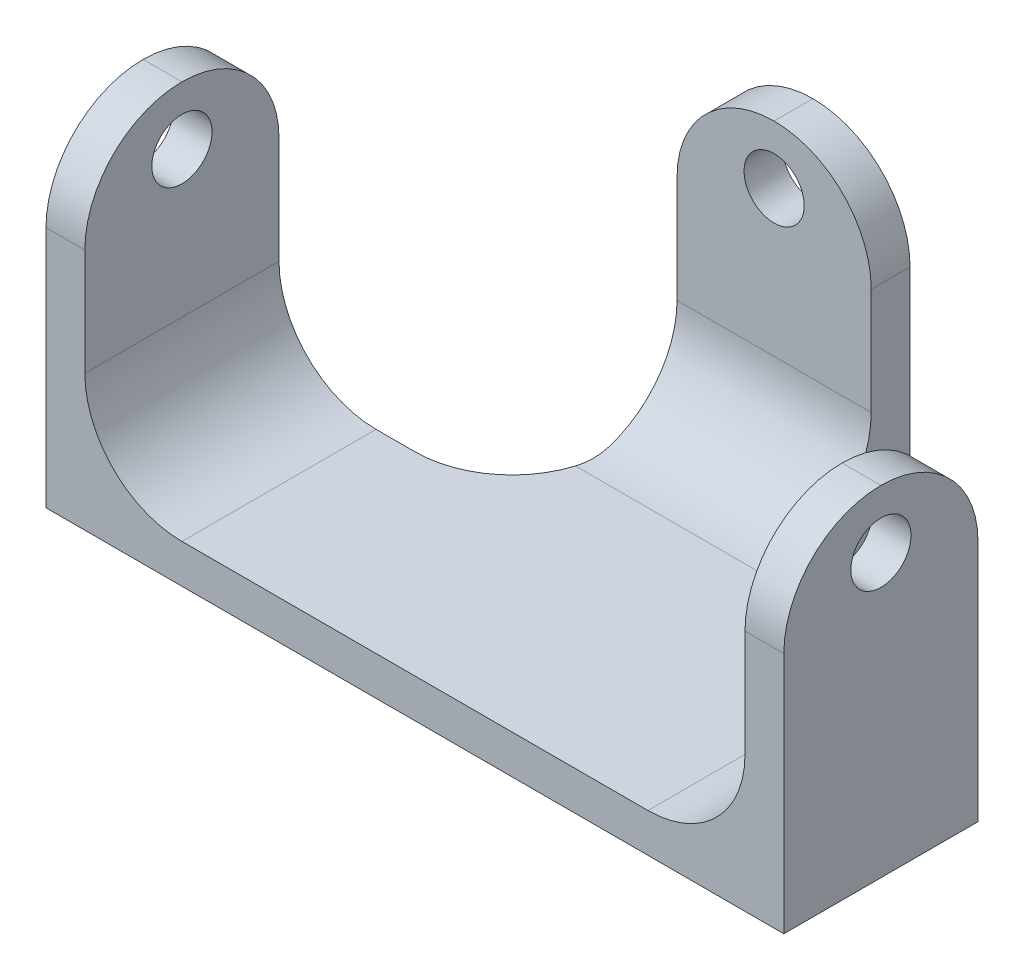
SolidWorks part; units mm, degrees
ref_plane "Front Plane" through (0, 0, 0) normal (0, 0, 1) x (1, 0, 0)
ref_plane "Top Plane" through (0, 0, 0) normal (0, 1, 0) x (1, 0, 0)
ref_plane "Right Plane" through (0, 0, 0) normal (1, 0, 0) x (0, 0, -1)
sketch "Sketch1" plane through (0, 0, 0) normal (0, 0, 1) x (1, 0, 0)
  line L0 (-10.6394, 6.8175) -> (-6.6394, 6.8175)
  line L1 (-6.6394, 6.8175) -> (-6.6394, -24.1825)
  line L2 (-6.6394, -24.1825) -> (61.3606, -24.1825)
  line L3 (61.3606, -24.1825) -> (61.3606, 6.8175)
  line L4 (61.3606, 6.8175) -> (65.3606, 6.8175)
  line L5 (65.3606, 6.8175) -> (65.3606, -28.1825)
  line L6 (65.3606, -28.1825) -> (-10.6394, -28.1825)
  line L7 (-10.6394, -28.1825) -> (-10.6394, 6.8175)
  point P6 (-2.0292, 4.2751)
  point P9 (-4.9784, 7.0209)
  point P10 (-6.6394, 6.8175)
  point P11 (-10.6394, -2.674)
  point P12 (-4.9106, -0.7757)
  point P13 (0.3775, -2.7757)
  point P14 (2.2419, 6.7497)
  dimension "D1" = 4
  dimension "D2" = 35
  dimension "D3" = 4
  dimension "D4" = 68
extrude "Boss-Extrude1" add sketch "Sketch1" along normal blind 62
sketch "Sketch2" plane through (0, -24.1825, 0) normal (0, 1, 0) x (1, 0, 0)
  line L0 (61.3606, 0) -> (-6.6394, 0) construction
  line L1 (-3.6394, 0) -> (58.3606, 0)
  line L2 (-3.6394, 0) -> (-3.6394, -4)
  line L3 (-3.6394, -4) -> (58.3606, -4)
  line L4 (58.3606, 0) -> (58.3606, -4)
  point P6 (27.3606, 0)
  point P7 (0, 0)
  point P9 (27.3606, 0)
  point P10 (28.3606, 0)
  dimension "D1" = 4
  dimension "D2" = 62
extrude "Boss-Extrude2" add sketch "Sketch2" along normal blind 31
sketch "Sketch4" plane through (-6.6394, 0, 0) normal (1, 0, 0) x (0, 0, -1)
  line L0 (-62, 6.8175) -> (0, 6.8175) construction
  circle A0 centre (-31, 0.8175) radius 3.1
  point P2 (-31, 6.8175)
  point P3 (0, 0)
  dimension "D1" = 6.2
  dimension "D2" = 6
extrude "Cut-Extrude1" cut sketch "Sketch4" against normal through all both and the other way through all
sketch "Sketch5" plane through (0, 0, 4) normal (0, 0, 1) x (1, 0, 0)
  line L0 (-3.6394, 6.8175) -> (58.3606, 6.8175) construction
  circle A0 centre (27.3606, 0.8175) radius 3.1
  point P2 (27.3606, 6.8175)
  point P3 (0, 0)
  dimension "D2" = 6.2
  dimension "D1" = 6
extrude "Cut-Extrude2" cut sketch "Sketch5" against normal through all
sketch "Sketch6" plane through (0, -28.1825, 0) normal (0, -1, 0) x (1, 0, 0)
  line L0 (65.3606, 62) -> (65.3606, 0) construction
  line L2 (-10.6394, 62) -> (65.3606, 62)
  line L3 (-10.6394, 62) -> (-10.6394, 41)
  line L4 (-10.6394, 41) -> (65.3606, 41)
  line L5 (65.3606, 62) -> (65.3606, 41)
  line L6 (17.3606, 21) -> (37.3606, 21) construction
  line L7 (-10.6394, 0) -> (17.3606, 0)
  line L8 (-10.6394, 0) -> (-10.6394, 21)
  line L9 (-10.6394, 21) -> (17.3606, 21)
  line L10 (17.3606, 0) -> (17.3606, 21)
  line L11 (65.3606, 0) -> (37.3606, 0)
  line L12 (65.3606, 0) -> (65.3606, 21)
  line L13 (65.3606, 21) -> (37.3606, 21)
  line L14 (37.3606, 0) -> (37.3606, 21)
  line L15 (17.3606, 21) -> (17.3606, 41) construction
  dimension "D1" = 20
extrude "Cut-Extrude3" cut sketch "Sketch6" against normal through all
fillet "Fillet1" radius 10 9 edges at (63.3606, 6.8175, 41) (63.3606, 6.8175, 21) (-8.6394, 6.8175, 21) (-8.6394, 6.8175, 41) (37.3606, 6.8175, 2) (17.3606, 6.8175, 2) (-6.6394, -24.1825, 31) (27.3606, -24.1825, 4) (61.3606, -24.1825, 31)
fillet "Fillet2" radius 10 2 edges at (17.3606, -26.1825, 21) (37.3606, -26.1825, 21)
equation "\"standWidth\"= 62"
equation "\"D1@Boss-Extrude1\"=\"standWidth\""
equation "\"standThickness\"=4"
equation "\"D1@Sketch1\"=\"standThickness\""
equation "\"standHeight\"= 35"
equation "\"D2@Sketch2\"=\"standWidth\""
equation "\"D1@Sketch2\"=\"standThickness\""
equation "\"D1@Boss-Extrude2\"=\"standHeight\"-\"standThickness\""
equation "\"holeFromTop\"=6"
equation "\"D2@Sketch4\"=\"holeFromTop\""
equation "\"D1@Sketch5\"=\"holeFromTop\""
equation "\"D2@Sketch1\"=\"standHeight\""
